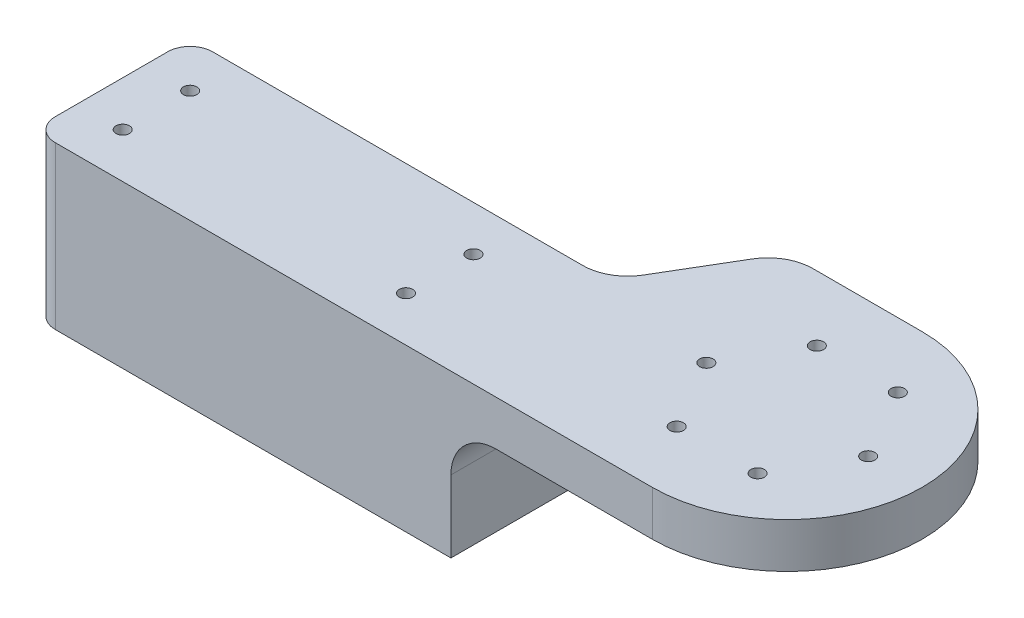
SolidWorks part; units mm, degrees
ref_plane "Front Plane" through (0, 0, 0) normal (1, 0, 0) x (0, 1, 0)
ref_plane "Top Plane" through (0, 0, 0) normal (0, 0, 1) x (0, 1, 0)
ref_plane "Right Plane" through (0, 0, 0) normal (0, 1, 0) x (-1, 0, 0)
sketch "Sketch1" plane through (0, 0, 0) normal (0, 1, 0) x (-1, 0, 0)
  line L0 (0, 35) -> (-44.8, 35)
  line L1 (0, 35) -> (88, 35)
  line L2 (0, 35) -> (0, 0)
  line L3 (0, 0) -> (88, 0)
  line L4 (93, 30) -> (93, 5)
  line L5 (20, 10) -> (83, 10) construction
  line L6 (20, 10) -> (20, 25) construction
  line L7 (20, 25) -> (83, 25) construction
  line L8 (83, 10) -> (83, 25) construction
  line L9 (-44.8, -25) -> (-14.8, -25)
  line L10 (-14.8, -25) -> (0, 0)
  line L11 (-14.8, 35) -> (-14.8, -25) construction
  arc A0 (88, 0) -> (93, 5) centre (88, 5) ccw
  arc A1 (88, 35) -> (93, 30) centre (88, 30) cw
  circle A2 centre (20, 25) radius 1.5
  circle A3 centre (83, 25) radius 1.5
  circle A4 centre (83, 10) radius 1.5
  circle A5 centre (20, 10) radius 1.5
  arc A6 (-44.8, 35) -> (-44.8, -25) centre (-44.8, 5) ccw
  circle A7 centre (-44.8, 5) radius 18 construction
  circle A8 centre (-62.8, 5) radius 1.5
  circle A9 centre (-53.8, 20.5885) radius 1.5
  circle A10 centre (-35.8, 20.5885) radius 1.5
  circle A11 centre (-26.8, 5) radius 1.5
  circle A12 centre (-35.8, -10.5885) radius 1.5
  circle A13 centre (-53.8, -10.5885) radius 1.5
  point P14 (93, 35)
  dimension "D6" = 5
  dimension "D7" = 3
  dimension "D8" = 60
  dimension "D11" = 36
  dimension "D12" = 3
  dimension "D1" = 15
  dimension "D2" = 10
  dimension "HipLength" = 93
  dimension "D3" = 20
  dimension "D4" = 10
  dimension "D5" = 10
  dimension "D9" = 30
  dimension "D10" = 14.8
  dimension "D13" = 6
extrude "Boss-Extrude2" add sketch "Sketch1" along normal blind 10 contours L0 A6 L9 L10 L2 A13 A12 A11 A10 A9 A8 | A1 L1 L2 L3 A0 L4 A5 A4 A3 A2 region at (35.8085, 0, 6.0346) region at (-46.3046, 0, 17.5)
extrude "Boss-Extrude3" add sketch "Sketch1<3>" against normal blind 26 contours A1 L1 L2 L3 A0 L4 A5 A4 A3 A2 region at (-46.3046, 0, 17.5)
sketch "Sketch1<3>" plane through (0, 0, 0) normal (0, 1, 0) x (-1, 0, 0) same geometry as "Sketch1"
fillet "Fillet1" radius 10 3 edges at (0, 0, 17.5) (0, 5, 0) (14.8, 5, -25)
equation "\"MotorDriverLength\"= 60mm"
equation "\"MotorLength\"= 60"
equation "\"MotorDriverWidth\"=44"
equation "\"MotorWidth\"= 37"
equation "\"InnerWallThickness\"=3"
equation "\"BatteryWidth\"= 60"
equation "\"OuterWallThickness\" = 6"
equation "\"CompartmentHeight\"=37"
equation "\"CompartmentWidth\"= \"MotorDriverLength\""
equation "\"MotorDiameter\"=37"
equation "\"BatteryHeight\"=24.2019"
equation "\"MotorDriverHeight\"=28"
equation "\"CircuitHeight\"=30"
equation "\"FanThickness\"= 10"
equation "\"FanHeight\"=50"
equation "\"MotorShaftHole\"=12"
equation "\"BearingBore\"=10"
equation "\"MinShinWidth\"= 20"
equation "\"ShinThickness\"=10"
equation "\"PivotDistance\"=30"
equation "\"ThighLength\"= 150"
equation "\"KneeLength\" =80"
equation "\"HipBore\"=27"
equation "\"ThighThickness\"=10"
equation "\"MaxBending\"=135"
equation "\"MaxStretchingAngle\"= 50"
equation "\"ThighJointDistance\"=157.485"
equation "\"ShinLength\"=120"
equation "\"BearingDiameter\"= 10"
equation "\"CircuitLength\"=50"
equation "\"ChessisInnerWidth\"= \"OuterWallThickness\" * 2 + \"MotorDriverLength\" + \"MotorDiameter\" + \"InnerWallThickness\" * 3 + \"CircuitLength\""
equation "\"ChessisHeight\"= \"BatteryHeight\" + 10 + \"InnerWallThickness\" + \"MotorDiameter\" + 10 + \"OuterWallThickness\" * 2"
equation "\"ChassisWidth\"= \"MotorDriverWidth\"*4+30"
